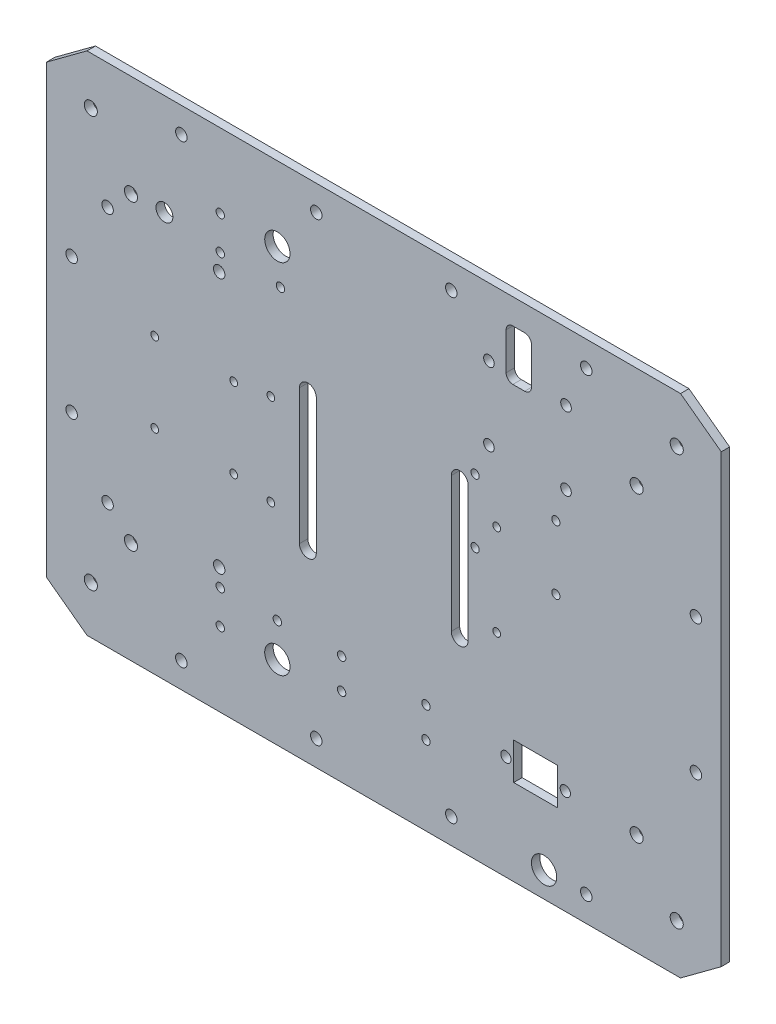
SolidWorks part; units mm, degrees
material "Thornel Mat VMA"
ref_plane "Front Plane" through (0, 0, 0) normal (0, 0, 1) x (1, 0, 0)
ref_plane "Top Plane" through (0, 0, 0) normal (0, 1, 0) x (1, 0, 0)
ref_plane "Right Plane" through (0, 0, 0) normal (1, 0, 0) x (0, 0, -1)
sketch "Sketch1" plane through (0, 0, 0) normal (0, 0, 1) x (1, 0, 0)
  line L0 (-127, 0) -> (127, 0) construction
  line L1 (0, -95.25) -> (0, 95.25) construction
  line L2 (-107.95, 0) -> (-107.95, 41.011) construction
  line L3 (-107.95, 41.011) -> (-95.25, 41.011) construction
  line L4 (-95.25, 41.011) -> (-79.9365, 52.3423) construction
  line L5 (-79.9365, 52.3423) -> (-79.9365, 76.2) construction
  line L6 (-79.9365, 76.2) -> (0, 76.2) construction
  line L7 (-95.25, 41.011) -> (-127, 83.9186) construction
  line L8 (-79.9365, 52.3423) -> (-111.6865, 95.25) construction
  line L9 (-111.6865, -95.25) -> (-127, -83.9186)
  line L10 (111.6865, -95.25) -> (127, -83.9186)
  line L11 (111.6865, 95.25) -> (127, 83.9186)
  line L12 (-87.5933, 46.6767) -> (-95.1475, 56.8856) construction
  line L13 (-95.1475, 56.8856) -> (-110.256, 77.3036) construction
  line L24 (127, -83.9186) -> (127, 83.9186)
  line L26 (111.6865, 95.25) -> (-111.6865, 95.25)
  line L27 (-111.6865, 95.25) -> (-127, 83.9186)
  line L28 (-127, 83.9186) -> (-127, -83.9186)
  line L30 (-111.6865, -95.25) -> (111.6865, -95.25)
  circle A0 centre (-95.1475, 56.8856) radius 2.4638
  circle A1 centre (-110.256, 77.3036) radius 2.4638
  circle A2 centre (110.256, 77.3036) radius 2.4638
  circle A3 centre (95.1475, 56.8856) radius 2.4638
  circle A4 centre (-110.256, -77.3036) radius 2.4638
  circle A5 centre (-95.1475, -56.8856) radius 2.4638
  circle A6 centre (110.256, -77.3036) radius 2.4638
  circle A7 centre (95.1475, -56.8856) radius 2.4638
  point P12 (0, 0)
  dimension "D1" = 190.5
  dimension "D2" = 254
  dimension "D3" = 19.05
  dimension "D4" = 19.05
  dimension "D5" = 12.7
  dimension "D6" = 19.05
  dimension "D7" = 143.5
  dimension "D8" = 12.7
  dimension "D9" = 25.4
extrude "Boss-Extrude1" add sketch "Sketch1" along normal blind 3.175
sketch "Sketch2" plane through (0, 0, 3.175) normal (0, 0, 1) x (1, 0, 0)
  line L0 (-127, 0) -> (127, 0) construction
  line L1 (-127, 83.9186) -> (-127, -83.9186) construction
  line L2 (127, -83.9186) -> (127, 83.9186) construction
  line L3 (57.15, 65.0875) -> (57.15, -65.0875) construction
  line L9 (48.895, -49.0837) -> (65.405, -49.0837)
  line L12 (57.15, 0) -> (57.15, 35.1373) construction
  line L19 (48.895, -49.0837) -> (48.895, -62.9267)
  line L20 (48.895, -62.9267) -> (65.405, -62.9267)
  line L21 (65.405, -49.0837) -> (65.405, -62.9267)
  circle A0 centre (68.326, -56.0052) radius 1.9431
  circle A1 centre (45.974, -56.0052) radius 1.9431
  point P20 (57.15, -56.0052)
  dimension "D10" = 3.8862
  dimension "D2" = 6.9215
  dimension "D3" = 16.51
  dimension "D5" = 69.85
  dimension "D9" = 13.843
  dimension "D11" = 11.176
extrude "Cut-Extrude1" cut sketch "Sketch2" against normal through all contours A1 | A0 | L19 L20 L21 L9 region at (68.326, -56.0052, 3.175) region at (45.974, -56.0052, 3.175)
sketch "Sketch3" plane through (0, 0, 3.175) normal (0, 0, 1) x (1, 0, 0)
  line L0 (0, 95.25) -> (0, -95.25) construction
  line L1 (111.6865, 95.25) -> (-111.6865, 95.25) construction
  line L2 (-111.6865, -95.25) -> (111.6865, -95.25) construction
  line L3 (127, 0) -> (-127, 0) construction
  line L4 (127, -83.9186) -> (127, 83.9186) construction
  line L5 (-127, 83.9186) -> (-127, -83.9186) construction
  circle A0 centre (-15.875, -65.5603) radius 1.5875
  circle A1 centre (15.875, -65.5603) radius 1.5875
  circle A2 centre (-15.875, -54.1303) radius 1.5875
  circle A3 centre (15.875, -54.1303) radius 1.5875
  dimension "D2" = 11.43
  dimension "D1" = 15.875
sketch "Sketch5" plane through (0, 0, 0) normal (0, 0, -1) x (-1, 0, 0)
  line L0 (-127, 0) -> (127, 0) construction
  line L1 (107.95, 52.136) -> (57.9501, 52.136) construction
  line L2 (107.95, 52.136) -> (107.95, -34.864) construction
  line L3 (107.95, -34.864) -> (57.9501, -34.864) construction
  line L4 (57.9501, 52.136) -> (57.9501, -34.864) construction
  line L5 (89.4966, 18.0341) -> (89.4966, -18.0339)
  line L6 (67.8946, 95.25) -> (67.8946, -95.25) construction
  line L7 (111.6865, -95.25) -> (-111.6865, -95.25) construction
  line L8 (0, 64.0679) -> (0, -49.8393) construction
  line L9 (-42.5, 17.2) -> (42.5, 17.2) construction
  line L10 (-42.5, 17.2) -> (-42.5, -17.2) construction
  line L11 (-42.5, -17.2) -> (42.5, -17.2) construction
  line L12 (42.5, 17.2) -> (42.5, -17.2) construction
  line L13 (-42.5, 17.2) -> (42.5, -17.2) construction
  line L14 (-42.5, -17.2) -> (42.5, 17.2) construction
  line L15 (46.8402, 60.96) -> (31.75, 60.96) construction
  line L16 (61.5446, -67.31) -> (-87.4336, -67.31) construction
  line L17 (-127, -83.9186) -> (-127, 83.9186) construction
  line L18 (40.0554, 67.31) -> (18.5661, 67.31) construction
  line L19 (-28.575, 25.4) -> (-28.575, -25.4) construction
  line L20 (127, 83.9186) -> (127, -83.9186) construction
  line L21 (-127, -83.9186) -> (-127, 83.9186) construction
  line L22 (-50.8, 76.2) -> (82.55, 76.2) construction
  line L23 (82.55, 76.2) -> (82.55, 57.216) construction
  line L25 (82.55, -68.4098) -> (82.55, 57.216) construction
  line L26 (127, 0) -> (-127, 0) construction
  line L27 (82.95, 0) -> (82.9501, -8419.0368) construction
  line L28 (-25.4, 25.4) -> (-25.4, -25.4)
  line L29 (-31.75, 25.4) -> (-31.75, -25.4)
  line L30 (28.575, 25.4) -> (28.575, -25.4) construction
  line L31 (25.4, 25.4) -> (25.4, -25.4)
  line L32 (31.75, 25.4) -> (31.75, -25.4)
  line L33 (71.3384, 0) -> (71.3384, 12.3782) construction
  line L34 (53.4794, 18.0341) -> (89.4966, 18.0341)
  line L35 (53.4794, 18.0341) -> (53.4794, -18.0339)
  line L36 (53.4794, -18.0339) -> (89.4966, -18.0339)
  line L37 (-46.0375, 66.675) -> (-55.5625, 66.675)
  line L38 (-46.0375, 66.675) -> (-46.0375, 85.725)
  line L39 (-46.0375, 85.725) -> (-55.5625, 85.725)
  line L40 (-50.8, 76.2) -> (-50.8, 95.25) construction
  line L41 (-55.5625, 66.675) -> (-55.5625, 85.725)
  line L42 (-46.0375, 66.675) -> (-55.5625, 85.725) construction
  line L43 (-46.0375, 85.725) -> (-55.5625, 66.675) construction
  line L47 (-127, -83.9186) -> (-127, 83.9186) construction
  line L48 (-111.6865, 95.25) -> (111.6865, 95.25) construction
  circle A0 centre (61.5446, -54.61) radius 1.5875
  circle A1 centre (61.5446, -67.31) radius 1.5875
  circle A2 centre (82.55, 57.216) radius 3.175
  circle A3 centre (-60.325, -85.725) radius 4.7625
  circle A4 centre (61.5446, 54.61) radius 1.5875
  circle A7 centre (40.0554, -67.31) radius 4.7625
  circle A8 centre (61.5446, 67.31) radius 1.5875
  circle A10 centre (40.0554, 67.31) radius 4.7625
  circle A12 centre (61.9506, 48.1355) radius 2.159
  circle A13 centre (103.9495, 48.1355) radius 2.159
  circle A14 centre (61.9506, -48.1355) radius 2.159
  circle A15 centre (103.9495, -48.1355) radius 2.159
  circle A17 centre (38.8861, 54.61) radius 1.5875
  circle A19 centre (40.0554, -54.61) radius 1.5875
  arc A20 (-25.4, 25.4) -> (-31.75, 25.4) centre (-28.575, 25.4) ccw
  arc A21 (-31.75, -25.4) -> (-25.4, -25.4) centre (-28.575, -25.4) ccw
  arc A22 (25.4, 25.4) -> (31.75, 25.4) centre (28.575, 25.4) cw
  arc A23 (31.75, -25.4) -> (25.4, -25.4) centre (28.575, -25.4) cw
  circle A24 centre (56.4794, 15.0341) radius 1.4478
  circle A25 centre (56.4794, -15.0341) radius 1.4478
  circle A26 centre (86.1974, -15.0341) radius 1.4478
  circle A27 centre (86.1974, 15.0341) radius 1.4478
  circle A28 centre (-42.5, 17.2) radius 1.4542
  circle A29 centre (-42.5, -17.2) radius 1.4541
  circle A30 centre (42.5, -17.2) radius 1.4541
  circle A31 centre (42.5, 17.2) radius 1.4542
  point P0 (82.95, 0)
  point P9 (0, 0)
  point P77 (-28.575, 0)
  point P84 (28.575, 0)
  point P89 (71.3384, 0)
  dimension "D10" = 6.35
  dimension "D15" = 2.9997
  dimension "D17" = 66.675
  dimension "D18" = 41.9989
  dimension "D21" = 47.1145
  dimension "D22" = 76.2
  dimension "D25" = 4.0005
  dimension "D45" = 2.8956
  dimension "D9" = 9.525
  dimension "D13" = 14.859
  dimension "D14" = 3
  dimension "D20" = 9.525
  dimension "D8" = 9.525
  dimension "D19" = 19.05
  dimension "D16" = 9.525
  dimension "D1" = 87.0001
  dimension "D2" = 49.9999
  dimension "D4" = 34.4
  dimension "D5" = 85
  dimension "D6" = 6.35
  dimension "D7" = 19.05
  dimension "D11" = 5.08
  dimension "D12" = 25.4
  dimension "D24" = 19.05
  dimension "D26" = 4.0005
  dimension "D38" = 50.8
  dimension "D39" = 6.35
  dimension "D40" = 28.575
  dimension "D41" = 36.0172
  dimension "D42" = 36.068
  dimension "D44" = 3
extrude "Cut-Extrude2" cut sketch "Sketch5" against normal through all contours A2 | A14 | A15 | A13 | A12 | L29 A21 L28 A20 | A23 L4 A22 L31 | A23 L32 A22 L4 | A27 | A24 | A25 | A26
sketch "Sketch6" plane through (0, 0, 0) normal (0, 0, -1) x (-1, 0, 0)
  line L0 (0, 0) -> (-135.1326, 0) construction
  line L1 (0, 0) -> (0, -95.25) construction
  line L2 (111.6865, -95.25) -> (-111.6865, -95.25) construction
  line L3 (-76.2, -95.25) -> (-76.2, -85.725) construction
  line L4 (117.475, 0) -> (117.475, -25.4) construction
  line L5 (127, 0) -> (-127, 0) construction
  line L6 (127, 83.9186) -> (127, -83.9186) construction
  circle A0 centre (-76.2, -85.725) radius 2.159
  circle A1 centre (-25.4, -85.725) radius 2.159
  circle A2 centre (25.4, -85.725) radius 2.159
  circle A3 centre (76.2, -85.725) radius 2.159
  circle A4 centre (76.2, 85.725) radius 2.159
  circle A5 centre (25.4, 85.725) radius 2.159
  circle A6 centre (-25.4, 85.725) radius 2.159
  circle A7 centre (-76.2, 85.725) radius 2.159
  circle A8 centre (117.475, -25.4) radius 2.159
  circle A9 centre (117.475, 25.4) radius 2.159
  circle A10 centre (-117.475, 25.4) radius 2.159
  circle A11 centre (-117.475, -25.4) radius 2.159
  dimension "D2" = 9.525
  dimension "D3" = 76.2
  dimension "D5" = 9.525
  dimension "D6" = 25.4
  dimension "D4" = 4
extrude "Cut-Extrude3" cut sketch "Sketch6" against normal through all
extrude "Cut-Extrude4" cut sketch "Sketch5<3>" against normal through all contours A28 | A29 | A31 | A30
sketch "Sketch5<3>" plane through (0, 0, 0) normal (0, 0, -1) x (-1, 0, 0) same geometry as "Sketch5"
extrude "Cut-Extrude5" cut sketch "Sketch5<4>" against normal through all contours A3 | A10 | A8 | A4 | A0 | A1 | A7 region at (60.325, -85.725, 0)
sketch "Sketch5<4>" plane through (0, 0, 0) normal (0, 0, -1) x (-1, 0, 0) same geometry as "Sketch5"
extrude "Cut-Extrude6" cut sketch "Sketch5<5>" against normal blind 2.54 contours A17
sketch "Sketch5<5>" plane through (0, 0, 0) normal (0, 0, -1) x (-1, 0, 0) same geometry as "Sketch5"
extrude "Cut-Extrude7" cut sketch "Sketch5<6>" against normal through all contours A17
sketch "Sketch5<6>" plane through (0, 0, 0) normal (0, 0, -1) x (-1, 0, 0) same geometry as "Sketch5"
extrude "Cut-Extrude8" cut sketch "Sketch5<7>" against normal blind 2.54 and the other way blind 7.62 contours L41 L37 L38 L39 | A19
sketch "Sketch5<7>" plane through (0, 0, 0) normal (0, 0, -1) x (-1, 0, 0) same geometry as "Sketch5"
extrude "Cut-Extrude9" cut sketch "Sketch5<9>" against normal through all contours A19
sketch "Sketch5<9>" plane through (0, 0, 0) normal (0, 0, -1) x (-1, 0, 0) same geometry as "Sketch5"
extrude "Cut-Extrude17" cut sketch "Sketch5<15>" against normal through all both and the other way through all contours L39 L41 L37 L38
sketch "Sketch5<15>" plane through (0, 0, 0) normal (0, 0, -1) x (-1, 0, 0) same geometry as "Sketch5"
fillet "Fillet1" radius 2.54 1 edges at (55.5625, 85.725, 1.5875) type face fillet first side face at (55.5625, 76.2, 1.5875) second side face at (50.8, 85.725, 1.5875)
fillet "Fillet2" radius 2.54 1 edges at (46.0375, 85.725, 1.5875) type face fillet first side face at (49.53, 85.725, 1.5875) second side face at (46.0375, 76.2, 1.5875)
fillet "Fillet3" radius 2.54 1 edges at (46.0375, 66.675, 1.5875) type face fillet first side face at (50.8, 66.675, 1.5875) second side face at (46.0375, 74.93, 1.5875)
fillet "Fillet4" radius 2.54 1 edges at (55.5625, 66.675, 1.5875) type face fillet first side face at (52.07, 66.675, 1.5875) second side face at (55.5625, 74.93, 1.5875)
sketch "Sketch9" plane through (0, 0, 3.175) normal (0, 0, 1) x (1, 0, 0)
  line L0 (127, -83.9186) -> (127, 83.9186) construction
  line L1 (34.37, 30.35) -> (64.77, 30.35) construction
  line L2 (34.37, 30.35) -> (34.37, 6.35) construction
  line L3 (34.37, 6.35) -> (64.77, 6.35) construction
  line L4 (64.77, 30.35) -> (64.77, 6.35) construction
  line L5 (-111.6865, -95.25) -> (111.6865, -95.25) construction
  line L6 (127, -83.9186) -> (127, 83.9186) construction
  line L7 (68.58, 69.85) -> (39.58, 69.85) construction
  line L8 (68.58, 69.85) -> (68.58, 42.35) construction
  line L9 (68.58, 42.35) -> (39.58, 42.35) construction
  line L10 (39.58, 69.85) -> (39.58, 42.35) construction
  line L11 (111.6865, 95.25) -> (-111.6865, 95.25) construction
  line L12 (127, 0) -> (0, 0) construction
  circle A0 centre (34.37, 30.35) radius 1.55
  circle A1 centre (64.77, 30.35) radius 1.55
  circle A2 centre (64.77, 6.35) radius 1.55
  circle A3 centre (34.37, 6.35) radius 1.55
  circle A4 centre (68.58, 69.85) radius 2
  circle A5 centre (39.58, 69.85) radius 2
  circle A6 centre (39.58, 42.35) radius 2
  circle A7 centre (68.58, 42.35) radius 2
  dimension "D1" = 3.1
  dimension "D6" = 4
  dimension "D2" = 24
  dimension "D3" = 30.4
  dimension "D4" = 62.23
  dimension "D5" = 101.6
  dimension "D7" = 29
  dimension "D8" = 27.5
  dimension "D9" = 58.42
  dimension "D10" = 25.4
extrude "Cut-Extrude18" cut sketch "Sketch9" against normal through all
extrude "Cut-Extrude19" cut sketch "Sketch3" against normal blind 976.122
